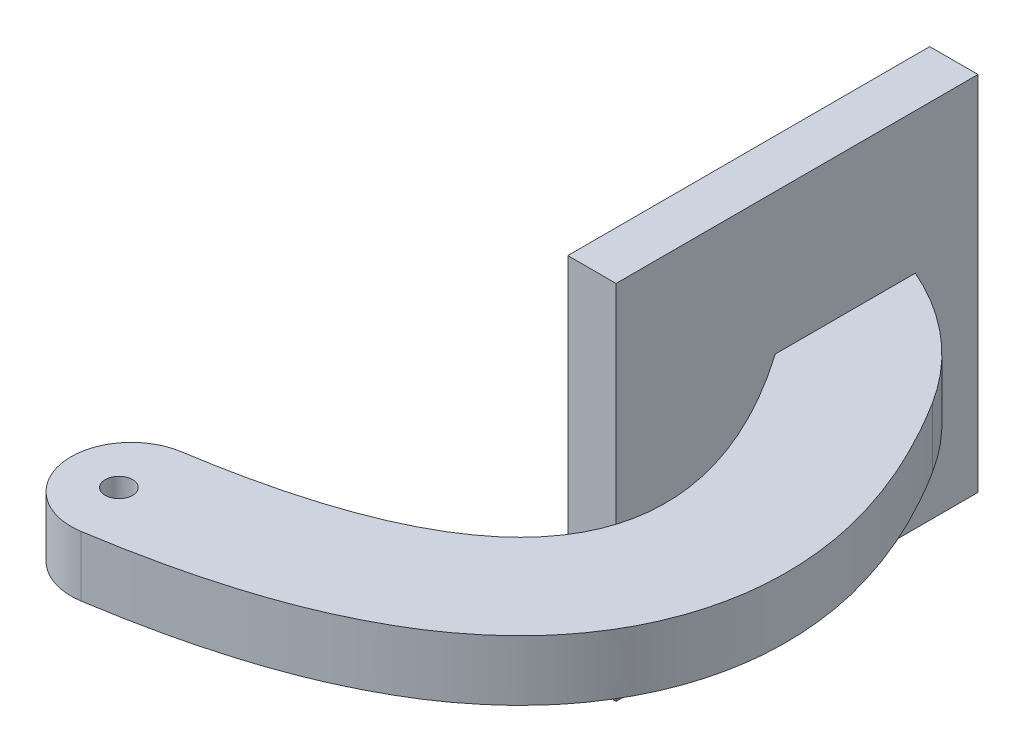
SolidWorks part; units mm, degrees
ref_plane "Front Plane" through (0, 0, 0) normal (0, 0, 1) x (1, 0, 0)
ref_plane "Top Plane" through (0, 0, 0) normal (0, 1, 0) x (1, 0, 0)
ref_plane "Right Plane" through (0, 0, 0) normal (1, 0, 0) x (0, 0, -1)
sketch "Sketch1" plane through (0, 0, 0) normal (0, 1, 0) x (1, 0, 0)
  line L0 (12.2998, 27.0428) -> (12.2998, 15.4349)
  arc A0 (-3.748, -26.0677) -> (-5.2818, -16.186) centre (-4.5149, -21.1269) cw
  arc A1 (22.317, 18.4446) -> (12.2998, 27.0428) centre (3.3664, 6.5008) ccw
  spline S0 degree 2 poles (22.317, 18.4446) (24.011, 15.7569) (26.568, 10.3292) (28.1991, 4.7061) (28.531, -0.2198) (28.1121, -4.2214) (26.9376, -8.1241) (25.039, -11.7201) (22.5533, -14.8576) (18.9085, -18.1555) (13.0095, -21.6106) (6.2321, -23.9838) (-0.1975, -25.518) (-3.748, -26.0677) knots 0.045026 0.045026 0.045026 0.134554 0.224083 0.313612 0.373298 0.432984 0.49267 0.552356 0.612042 0.70157 0.820942 0.910471 1 1 1
  spline S1 degree 2 poles (12.2998, 15.4349) (30.534, -10.6094) (-5.2818, -16.186) knots 0 0 0 1 1 1
  point P1 (12.2998, 21.2388)
  point P3 (-148.4979, 106.4588)
extrude "Boss-Extrude1" add sketch "Sketch1" along normal blind 2.5 and the other way blind 2.5
sketch "Sketch2" plane through (12.2998, 0, 0) normal (-1, 0, 0) x (0, 0, 1)
  line L0 (-32.2369, -15.8344) -> (-2.2369, -15.8344)
  line L1 (-32.2369, -15.8344) -> (-32.2369, 14.1656)
  line L2 (-32.2369, 14.1656) -> (-2.2369, 14.1656)
  line L3 (-2.2369, -15.8344) -> (-2.2369, 14.1656)
  point P4 (-17.2369, -0.8344)
extrude "Boss-Extrude2" add sketch "Sketch2" along normal blind 4
sketch "Sketch3" plane through (0, -2.5, 0) normal (0, -1, 0) x (1, 0, 0)
  circle A0 centre (-5.3234, 21.3457) radius 1.1359
extrude "Cut-Extrude1" cut sketch "Sketch3" against normal blind 5 and the other way through all
ref_point "Point1"
